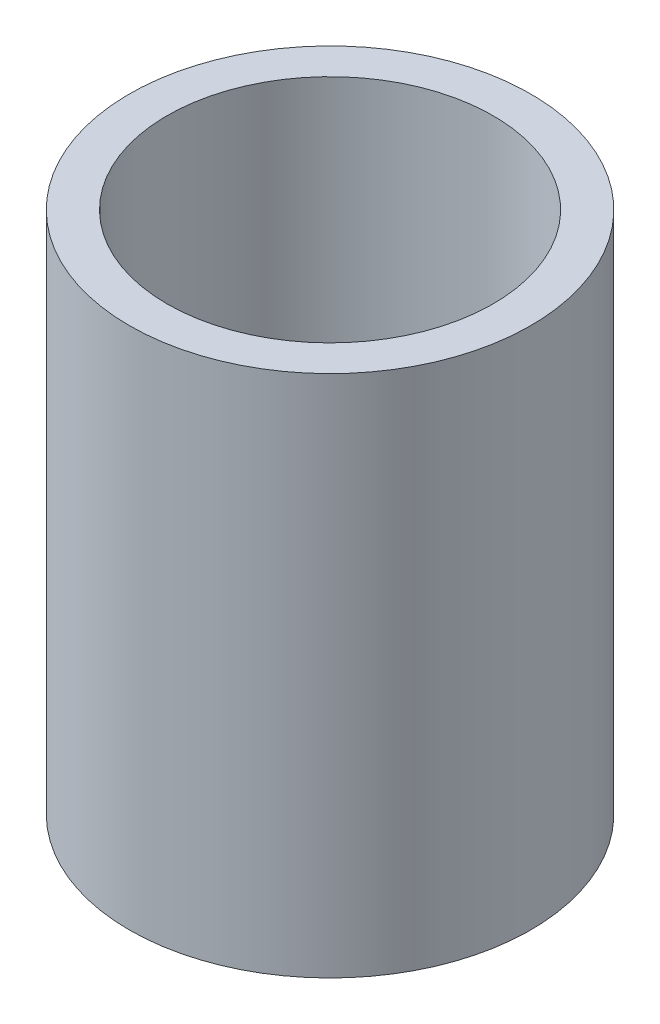
SolidWorks part; units mm, degrees
material "PVC Rigid"
ref_plane "Front Plane" through (0, 0, 0) normal (0, 0, 1) x (1, 0, 0)
ref_plane "Top Plane" through (0, 0, 0) normal (0, 1, 0) x (1, 0, 0)
ref_plane "Right Plane" through (0, 0, 0) normal (1, 0, 0) x (0, 0, -1)
sketch "Sketch1" plane through (0, 0, 0) normal (0, 1, 0) x (1, 0, 0)
  circle A0 centre (0, 0) radius 16.51
  circle A1 centre (0, 0) radius 20.32
  dimension "D1" = 40.64
  dimension "D2" = 33.02
extrude "Boss-Extrude1" add sketch "Sketch1" along normal blind 53
